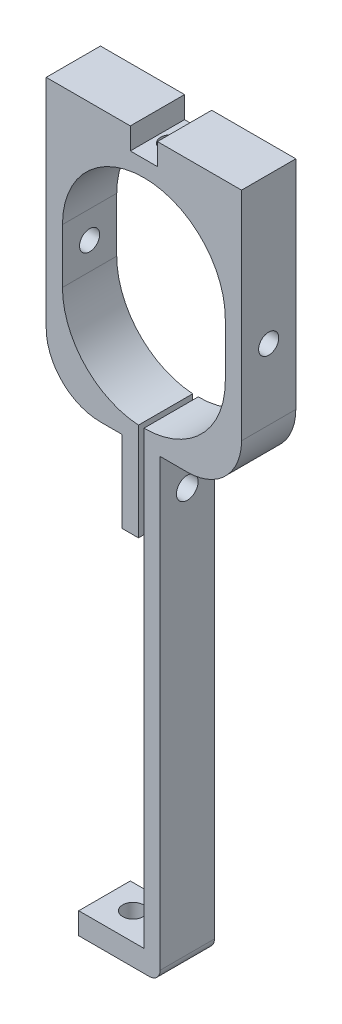
SolidWorks part; units mm, degrees
ref_plane "Front Plane" through (0, 0, 0) normal (0, 0, 1) x (1, 0, 0)
ref_plane "Top Plane" through (0, 0, 0) normal (0, 1, 0) x (1, 0, 0)
ref_plane "Right Plane" through (0, 0, 0) normal (1, 0, 0) x (0, 0, -1)
sketch "Sketch2" plane through (0, 0, 0) normal (0, 0, 1) x (1, 0, 0)
  line L0 (15, 0) -> (30, 0)
  line L1 (0, 0) -> (14, 0)
  line L2 (0, 0) -> (0, 40)
  line L3 (0, 40) -> (30, 40)
  line L4 (30, 0) -> (30, 40)
  line L13 (14, 0) -> (14, -80)
  line L14 (14, -80) -> (15, -80)
  line L15 (15, -80) -> (15, 0)
  line L16 (18, -3) -> (33, -3)
  line L17 (33, -3) -> (33, 43)
  line L18 (-3, 43) -> (33, 43)
  line L19 (-3, -3) -> (-3, 43)
  line L20 (-3, -3) -> (11, -3)
  line L21 (11, -3) -> (11, -83)
  line L22 (11, -83) -> (18, -83)
  line L23 (18, -83) -> (18, -3)
  dimension "D1" = 40
  dimension "D2" = 30
  dimension "D3" = 1
  dimension "D4" = 80
  dimension "D5" = 14
  dimension "D6" = 3
extrude "Boss-Extrude2" add sketch "Sketch2" along normal blind 10
sketch "Sketch5" plane through (0, 0, 10) normal (0, 0, 1) x (1, 0, 0)
  line L0 (4, -3) -> (4, -18) construction
  line L5 (15, -80) -> (15, -85.4078) construction
  line L7 (-3, -3) -> (11, -3) construction
  line L9 (4, -18) -> (15, -18)
  line L10 (4, -18) -> (4, -85.4078)
  line L11 (4, -85.4078) -> (15, -85.4078)
  line L12 (15, -18) -> (15, -85.4078)
  dimension "D1" = 15
extrude "Cut-Extrude2" cut sketch "Sketch5" against normal through all both and the other way through all
sketch "Sketch9" plane through (0, 0, 0) normal (0, 0, -1) x (-1, 0, 0)
  line L0 (-15, 43) -> (-15, 93.655) construction
  line L1 (-33, 43) -> (3, 43) construction
  line L2 (-35, 43) -> (5, 43)
  line L3 (5, 43) -> (25, 43) construction
  line L4 (25, 43) -> (25, 53) construction
  line L5 (5, 43) -> (20.6456, 50.8228)
  line L6 (25, 53) -> (45, 53) construction
  line L7 (45, 53) -> (45, 73) construction
  line L9 (45, 85.4264) -> (45, 113)
  line L10 (3, 43) -> (3, -3) construction
  line L11 (-75, 53) -> (-75, 73) construction
  line L12 (-55, 53) -> (-75, 53) construction
  line L13 (-70, 85.4264) -> (-70, 113)
  line L14 (-55, 43) -> (-55, 53) construction
  line L15 (-35, 43) -> (-55, 43) construction
  line L16 (-75, 85.4264) -> (-75, 113)
  line L17 (-58.4424, 56.4424) -> (-66.2132, 64.2132)
  line L18 (-35, 43) -> (-50.6456, 50.8228)
  line L19 (-54.9069, 59.978) -> (-62.6777, 67.7487)
  line L20 (-33.8197, 48) -> (-48.4096, 55.295)
  line L21 (-33.8197, 48) -> (3.8197, 48)
  line L22 (3.8197, 48) -> (18.4096, 55.295)
  line L24 (40, 85.4264) -> (40, 113)
  line L25 (-75, 113) -> (-70, 113)
  line L26 (40, 113) -> (45, 113)
  line L27 (40, 85.4264) -> (18.4096, 55.295)
  line L28 (20.6456, 50.8228) -> (36.2132, 64.2132)
  line L29 (45, 85.4264) -> (36.2132, 64.2132)
  line L31 (24.9069, 59.978) -> (32.6777, 67.7487) construction
  line L32 (28.4424, 56.4424) -> (36.2132, 64.2132) construction
  arc A2 (-58.4424, 56.4424) -> (-50.6456, 50.8228) centre (-37.2292, 77.6556) ccw
  arc A3 (-66.2132, 64.2132) -> (-75, 85.4264) centre (-45, 85.4264) cw
  arc A4 (-62.6777, 67.7487) -> (-70, 85.4264) centre (-45, 85.4264) cw
  arc A5 (-54.9069, 59.978) -> (-48.4096, 55.295) centre (-37.2292, 77.6556) ccw
  arc A8 (40, 85.4264) -> (32.6777, 67.7487) centre (15, 85.4264) cw construction
  arc A9 (24.9069, 59.978) -> (18.4096, 55.295) centre (7.2292, 77.6556) cw construction
  arc A10 (28.4424, 56.4424) -> (20.6456, 50.8228) centre (7.2292, 77.6556) cw construction
  arc A11 (45, 85.4264) -> (36.2132, 64.2132) centre (15, 85.4264) cw construction
  dimension "D7" = 21.2132
  dimension "D1" = 20
  dimension "D2" = 20
  dimension "D3" = 10
  dimension "D4" = 20
  dimension "D5" = 20
  dimension "D6" = 40
  dimension "D8" = 5
  dimension "D9" = 20.5342
  dimension "D10" = 15.6456
sketch "Sketch16" plane through (11, 0, 0) normal (-1, 0, 0) x (0, 0, 1)
  line L0 (0, -18) -> (10, -3) construction
  line L1 (0, -3) -> (10, -18) construction
  circle A0 centre (5, -10.5) radius 1.85
  dimension "D1" = 3.7
extrude "Cut-Extrude3" cut sketch "Sketch16" against normal through all both and the other way through all
fillet "Fillet16" radius 15 4 edges at (0, 40, 5) (30, 40, 5) (0, 0, 5) (30, 0, 5)
sketch "Sketch41" plane through (18, 0, 0) normal (1, 0, 0) x (0, 0, -1)
  line L0 (0, -83) -> (-20, -83) construction
  circle A0 centre (-20, -83) radius 20
  dimension "D1" = 20
sketch "Sketch44" plane through (0, 0, 0) normal (0, 0, -1) x (-1, 0, 0)
sketch "Sketch45" plane through (-3, 0, 0) normal (-1, 0, 0) x (0, 0, 1)
  line L0 (0, 43) -> (10, -3) construction
  line L1 (10, -3) -> (10, 43) construction
  line L2 (10, 43) -> (0, -3) construction
  circle A0 centre (5, 20) radius 1.85
  dimension "D1" = 3.7
extrude "Cut-Extrude20" cut sketch "Sketch45" against normal through all both and the other way through all
sketch "Sketch46" plane through (0, 43, 0) normal (0, 1, 0) x (1, 0, 0)
  line L0 (-3, -10) -> (33, 0) construction
  line L1 (33, 0) -> (-3, 0) construction
  line L2 (-3, 0) -> (33, -10) construction
  line L3 (33, -10) -> (33, 0) construction
  circle A0 centre (15, -5) radius 1.85
  dimension "D1" = 3.7
sketch "Sketch48" plane through (-3, 0, 0) normal (-1, 0, 0) x (0, 0, 1)
  line L0 (5, 43) -> (5, 38.4589) construction
  line L1 (10, 43) -> (0, 43) construction
  line L3 (7, 45) -> (3, 45)
  line L4 (7, 45) -> (7, 41)
  line L5 (7, 41) -> (3, 41)
  line L6 (3, 45) -> (3, 41)
  line L7 (7, 45) -> (3, 41) construction
  line L8 (7, 41) -> (3, 45) construction
  dimension "D1" = 4
  dimension "D2" = 4
sketch "Sketch52" plane through (0, -83, 0) normal (0, -1, 0) x (1, 0, 0)
  line L1 (18, 10) -> (3, 10)
  line L2 (18, 10) -> (18, 0)
  line L3 (18, 0) -> (3, 0)
  line L4 (3, 10) -> (3, 0)
  dimension "D1" = 15
  dimension "D2" = 10
extrude "Boss-Extrude25" add sketch "Sketch52" along normal blind 4
fillet "Fillet17" radius 10 2 edges at (-3, -3, 5) (33, -3, 5)
fillet "Fillet18" radius 2 1 edges at (18, -87, 5)
sketch "Sketch53" plane through (0, -87, 0) normal (0, -1, 0) x (1, 0, 0)
  line L0 (16, 5) -> (0, 5) construction
  line L1 (16, 0) -> (16, 10) construction
  line L2 (3, 10) -> (3, 0) construction
  circle A0 centre (8, 5) radius 1.9
  dimension "D1" = 3.8
  dimension "D2" = 5
extrude "Cut-Extrude25" cut sketch "Sketch53" against normal blind 10
sketch "Sketch54" plane through (3, 0, 0) normal (-1, 0, 0) x (0, 0, 1)
  line L0 (10, -87) -> (0, -87) construction
  line L2 (0, -83) -> (0.5, -83)
  line L3 (0, -83) -> (0, -87)
  line L4 (0, -87) -> (0.5, -87)
  line L5 (0.5, -83) -> (0.5, -87)
  line L6 (10, -83) -> (9.5, -83)
  line L7 (10, -83) -> (10, -87)
  line L8 (10, -87) -> (9.5, -87)
  line L9 (9.5, -83) -> (9.5, -87)
  dimension "D1" = 0.5
  dimension "D2" = 0.5
sketch "Sketch55" plane through (3, 0, 0) normal (-1, 0, 0) x (0, 0, 1)
  line L0 (10, -87) -> (0, -87) construction
  line L1 (0, -83) -> (0.5, -83)
  line L2 (0, -83) -> (0, -87)
  line L3 (0, -87) -> (0.5, -87)
  line L4 (0.5, -83) -> (0.5, -87)
  dimension "D1" = 0.5
extrude "Cut-Extrude28" cut sketch "Sketch55" against normal blind 10
sketch "Sketch56" plane through (-3, 0, 0) normal (-1, 0, 0) x (0, 0, 1)
  line L1 (10, 43) -> (0, 43)
  line L2 (10, 43) -> (10, 47)
  line L3 (10, 47) -> (0, 47)
  line L4 (0, 43) -> (0, 47)
  dimension "D1" = 4
extrude "Boss-Extrude26" add sketch "Sketch56" against normal blind 36
sketch "Sketch57" plane through (0, 47, 0) normal (0, 1, 0) x (1, 0, 0)
  line L0 (-3, -5) -> (33, -5) construction
  line L1 (-3, -10) -> (-3, 0) construction
  line L2 (33, -10) -> (33, 0) construction
  line L3 (33, -5) -> (15, 0) construction
  line L4 (33, 0) -> (-3, 0) construction
  line L5 (15, 0) -> (15, -10) construction
  line L6 (33, -10) -> (-3, -10) construction
  circle A0 centre (15, -5) radius 1.9
  dimension "D1" = 3.8
extrude "Cut-Extrude29" cut sketch "Sketch57" against normal blind 36
sketch "Sketch59" plane through (0, 47, 0) normal (0, 1, 0) x (1, 0, 0)
  line L0 (-3, 0) -> (33, -10) construction
  line L1 (33, -10) -> (33, 0) construction
  line L2 (33, 0) -> (-3, -10) construction
  line L3 (33, 0) -> (-3, 0) construction
  line L8 (-2.2175, -7.8648) -> (33, -2.005) construction
  line L9 (-2.4462, -5) -> (32.4462, -5) construction
  line L10 (17.5, -10) -> (12.5, -10)
  line L11 (17.5, -10) -> (17.5, 0)
  line L12 (17.5, 0) -> (12.5, 0)
  line L13 (12.5, -10) -> (12.5, 0)
  line L14 (17.5, -10) -> (12.5, 0) construction
  line L15 (17.5, 0) -> (12.5, -10) construction
  point P4 (15, -5)
  point P13 (15, -5)
  dimension "D1" = 2.8739
  dimension "D2" = 5
extrude "Cut-Extrude31" cut sketch "Sketch59" against normal blind 4
sketch "Sketch60" plane through (18, 0, 0) normal (1, 0, 0) x (0, 0, -1)
  line L0 (-5, -8.65) -> (-5, -12.35) construction
  line L1 (-5, -12.35) -> (-3.15, -10.5) construction
  line L2 (-3.15, -10.5) -> (-6.85, -10.5) construction
  circle A0 centre (-5, -10.5) radius 1.85 construction
  circle A1 centre (-5, -10.5) radius 2
  dimension "D1" = 4
extrude "Cut-Extrude32" cut sketch "Sketch60" against normal through all both and the other way through all
